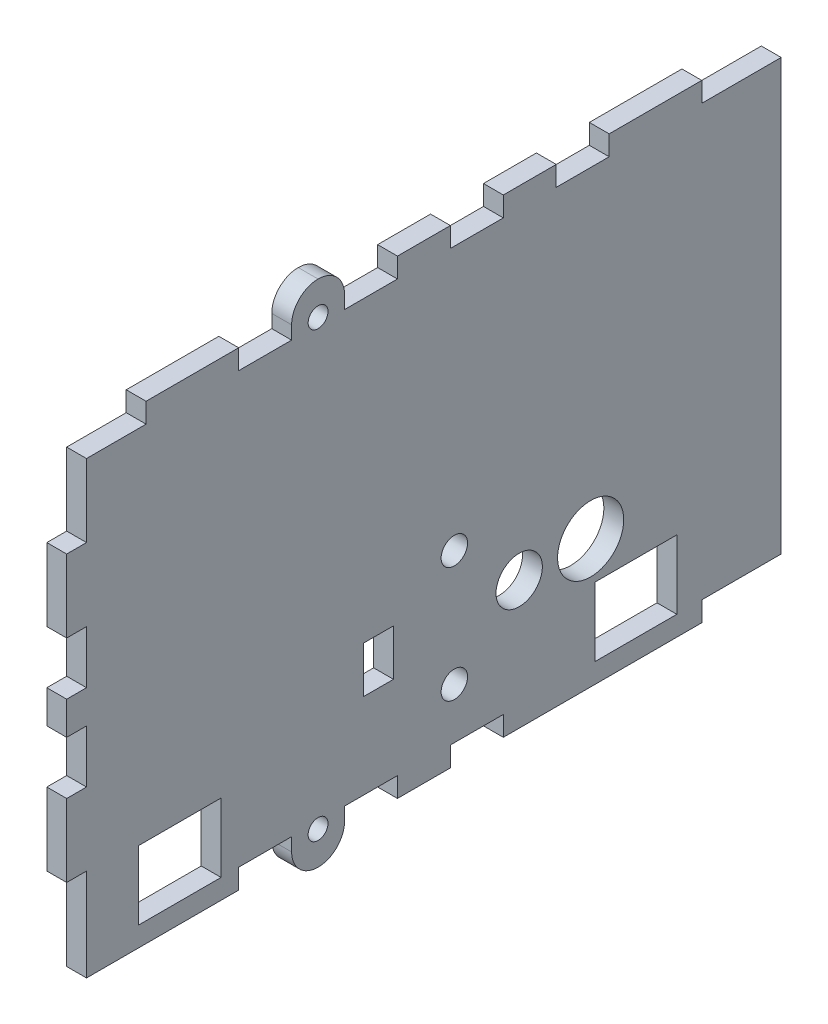
SolidWorks part; units mm, degrees
material "Balsa"
ref_plane "Alzado" through (0, 0, 0) normal (0, 0, 1) x (1, 0, 0)
ref_plane "Planta" through (0, 0, 0) normal (0, 1, 0) x (1, 0, 0)
ref_plane "Vista lateral" through (0, 0, 0) normal (1, 0, 0) x (0, 0, -1)
sketch "Croquis1" plane through (0, 0, 0) normal (1, 0, 0) x (0, 0, -1)
  line L1 (-54, -35.5) -> (54, -35.5)
  line L2 (-54, -35.5) -> (-54, 35.5)
  line L3 (-54, 35.5) -> (54, 35.5)
  line L4 (54, -35.5) -> (54, 35.5)
  line L5 (-54, -35.5) -> (54, 35.5) construction
  line L6 (-54, 35.5) -> (54, -35.5) construction
  point P0 (0, 0)
  dimension "D1" = 108
  dimension "D2" = 71
extrude "Saliente-Extruir1" add sketch "Croquis1" along normal mid plane 3
sketch "Croquis2" plane through (-1.5, 0, 0) normal (-1, 0, 0) x (0, 0, 1)
  line L1 (-42, -32.5) -> (-54, -32.5)
  line L2 (-42, -32.5) -> (-42, -35.5)
  line L3 (-42, -35.5) -> (-54, -35.5)
  line L4 (-54, -32.5) -> (-54, -35.5)
  line L9 (-12, -32.5) -> (-4, -32.5)
  line L25 (-54, 0) -> (54, 0) construction
  line L30 (-54, -35.5) -> (-54, 35.5) construction
  line L31 (54, 35.5) -> (54, -35.5) construction
  line L32 (54, 32.5) -> (54, 35.5)
  line L33 (42, 35.5) -> (54, 35.5)
  line L34 (42, 32.5) -> (42, 35.5)
  line L35 (42, 32.5) -> (54, 32.5)
  line L36 (28, 32.5) -> (28, 35.5)
  line L37 (20, 35.5) -> (28, 35.5)
  line L38 (20, 32.5) -> (20, 35.5)
  line L39 (20, 32.5) -> (28, 32.5)
  line L40 (12, 32.5) -> (12, 35.5)
  line L41 (4, 35.5) -> (12, 35.5)
  line L42 (4, 32.5) -> (4, 35.5)
  line L43 (4, 32.5) -> (12, 32.5)
  line L44 (-4, 32.5) -> (-4, 35.5)
  line L45 (-12, 35.5) -> (-4, 35.5)
  line L46 (-12, 32.5) -> (-12, 35.5)
  line L47 (-12, 32.5) -> (-4, 32.5)
  line L48 (-20, 32.5) -> (-20, 35.5)
  line L49 (-28, 35.5) -> (-20, 35.5)
  line L50 (-28, 32.5) -> (-28, 35.5)
  line L51 (-28, 32.5) -> (-20, 32.5)
  line L52 (-54, 32.5) -> (-54, 35.5)
  line L53 (-42, 35.5) -> (-54, 35.5)
  line L54 (-42, 32.5) -> (-42, 35.5)
  line L55 (-42, 32.5) -> (-54, 32.5)
  line L56 (-12, -32.5) -> (-12, -35.5)
  line L57 (-12, -35.5) -> (-4, -35.5)
  line L58 (-4, -32.5) -> (-4, -35.5)
  line L59 (4, -32.5) -> (12, -32.5)
  line L60 (4, -32.5) -> (4, -35.5)
  line L61 (4, -35.5) -> (12, -35.5)
  line L62 (12, -32.5) -> (12, -35.5)
  line L63 (20, -32.5) -> (28, -32.5)
  line L64 (20, -32.5) -> (20, -35.5)
  line L65 (20, -35.5) -> (28, -35.5)
  line L66 (28, -32.5) -> (28, -35.5)
extrude "Cortar-Extruir1" cut sketch "Croquis2" against normal blind 3
sketch "Croquis6" plane through (-1.5, 0, 0) normal (-1, 0, 0) x (0, 0, 1)
  line L0 (54, 32.5) -> (54, -35.5) construction
  line L1 (51, -21.5) -> (54, -21.5)
  line L2 (51, -21.5) -> (51, -35.5)
  line L3 (51, -35.5) -> (54, -35.5)
  line L4 (54, -21.5) -> (54, -35.5)
  line L5 (51, -2.5) -> (54, -2.5)
  line L6 (51, -2.5) -> (51, -10.5)
  line L7 (51, -10.5) -> (54, -10.5)
  line L8 (54, -2.5) -> (54, -10.5)
  line L9 (51, -10.5) -> (54, -10.5) construction
  line L10 (51, 10.5) -> (54, 10.5) construction
  line L11 (51, 2.5) -> (54, 2.5)
  line L12 (51, 2.5) -> (51, 10.5)
  line L13 (51, 10.5) -> (54, 10.5)
  line L14 (54, 2.5) -> (54, 10.5)
  line L16 (51, 21.5) -> (54, 21.5)
  line L17 (51, 21.5) -> (51, 35.5)
  line L18 (51, 35.5) -> (54, 35.5)
  line L19 (54, 21.5) -> (54, 35.5)
extrude "Cortar-Extruir3" cut sketch "Croquis6" against normal blind 3
sketch "Croquis8" plane through (-1.5, 0, 0) normal (-1, 0, 0) x (0, 0, 1)
  line L1 (12, 35.5) -> (20, 35.5)
  line L2 (12, 35.5) -> (12, 38.5)
  line L3 (12, 38.5) -> (20, 38.5)
  line L4 (20, 35.5) -> (20, 38.5)
  dimension "D1" = 3
extrude "Saliente-Extruir2" add sketch "Croquis8" against normal blind 3
fillet "Redondeo2" radius 4 2 edges at (0, 38.5, 20) (0, 38.5, 12)
sketch "Croquis9" plane through (-1.5, 0, 0) normal (-1, 0, 0) x (0, 0, 1)
  line L0 (12, 33.5) -> (20, 33.5) construction
  line L1 (12, 32.5) -> (12, 34.5) construction
  line L2 (20, 34.5) -> (20, 32.5) construction
  circle A0 centre (16, 33.5) radius 1.5
  dimension "D1" = 3
extrude "Cortar-Extruir5" cut sketch "Croquis9" against normal blind 3
mirror "Simetría1" about plane through (0, 0, 0) normal (0, 1, 0) of "Redondeo2", "Cortar-Extruir5", "Saliente-Extruir2"
sketch "Croquis12" plane through (-1.5, 0, 0) normal (-1, 0, 0) x (0, 0, 1)
  line L5 (43.1407, -22.1055) -> (30.6593, -22.1055)
  line L6 (43.1407, -22.1055) -> (43.1407, -32.5055)
  line L7 (43.1407, -32.5055) -> (30.6593, -32.5055)
  line L8 (30.6593, -22.1055) -> (30.6593, -32.5055)
  line L9 (-38.2299, -32.5055) -> (-25.8739, -32.5055)
  line L10 (-38.2299, -32.5055) -> (-38.2299, -22.1055)
  line L11 (-38.2299, -22.1055) -> (-25.8739, -22.1055)
  line L12 (-25.8739, -32.5055) -> (-25.8739, -22.1055)
  dimension "D1" = 10.4
  dimension "D2" = 10.4
extrude "Cortar-Extruir7" cut sketch "Croquis12" against normal blind 10
sketch "Croquis10" plane through (-1.5, 0, 0) normal (-1, 0, 0) x (0, 0, 1)
  line L0 (-25.2, -16.1) -> (9.1, -16.1) construction
  line L1 (4.6, -19.6) -> (9.1, -19.6)
  line L2 (4.6, -19.6) -> (4.6, -12.6)
  line L3 (4.6, -12.6) -> (9.1, -12.6)
  line L4 (9.1, -19.6) -> (9.1, -12.6)
  line L5 (-4.6, -24.85) -> (-4.6, -16.1) construction
  line L6 (-4.6, -16.1) -> (-4.6, -7.35) construction
  line L7 (-25.2, -49.1) -> (-59.5051, -49.1) construction
  line L8 (-25.8739, -32.5055) -> (-38.2299, -22.1055) construction
  line L12 (-42, -32.5) -> (-54, -32.5) construction
  circle A0 centre (-25.2, -16.1) radius 4.6
  circle A1 centre (-14.4, -16.1) radius 3.5
  circle A2 centre (-4.6, -24.85) radius 2
  circle A3 centre (-4.6, -7.35) radius 2
  dimension "D5" = 4
  dimension "D6" = 4
  dimension "D12" = 8.75
  dimension "D1" = 17.5
  dimension "D2" = 9.2
  dimension "D3" = 4.5
  dimension "D4" = 7
  dimension "D7" = 20.6
  dimension "D8" = 9.8
  dimension "D9" = 4.6
  dimension "D11" = 33
  dimension "20" = 16.4
extrude "Cortar-Extruir6" cut sketch "Croquis10" against normal blind 10 contours A0 | A1 | A1 | A2 | L1 L4 L3 L2 | A3 region at (-1.5, -16.1, 6.85) region at (-1.5, -16.1, -25.2) region at (-1.5, -16.1, -14.4) region at (-1.5, -24.85, -4.6)
sketch "Croquis14" plane through (1.5, 0, 0) normal (1, 0, 0) x (0, 0, -1)
  line L48 (-20, -32.5) -> (-20, -34.5)
  line L49 (-12, -34.5) -> (-12, -32.5)
  line L50 (-12, -32.5) -> (-4, -32.5)
  line L51 (-4, -32.5) -> (-4, -35.5)
  line L52 (-4, -35.5) -> (4, -35.5)
  line L53 (4, -35.5) -> (4, -32.5)
  line L54 (4, -32.5) -> (12, -32.5)
  line L55 (12, -32.5) -> (12, -35.5)
  line L56 (12, -35.5) -> (42, -35.5)
  line L57 (42, -35.5) -> (42, -32.5)
  line L58 (42, -32.5) -> (54, -32.5)
  line L59 (54, -32.5) -> (54, 32.5)
  line L60 (54, 32.5) -> (42, 32.5)
  line L61 (42, 32.5) -> (42, 35.5)
  line L62 (42, 35.5) -> (28, 35.5)
  line L63 (28, 35.5) -> (28, 32.5)
  line L64 (28, 32.5) -> (20, 32.5)
  line L65 (20, 32.5) -> (20, 35.5)
  line L66 (20, 35.5) -> (12, 35.5)
  line L67 (12, 35.5) -> (12, 32.5)
  line L68 (12, 32.5) -> (4, 32.5)
  line L69 (4, 32.5) -> (4, 35.5)
  line L70 (4, 35.5) -> (-4, 35.5)
  line L71 (-4, 35.5) -> (-4, 32.5)
  line L72 (-4, 32.5) -> (-12, 32.5)
  line L73 (-12, 32.5) -> (-12, 34.5)
  line L74 (-20, 34.5) -> (-20, 32.5)
  line L75 (-20, 32.5) -> (-28, 32.5)
  line L76 (-28, 32.5) -> (-28, 35.5)
  line L77 (-28, 35.5) -> (-42, 35.5)
  line L78 (-42, 35.5) -> (-42, 32.5)
  line L79 (-42, 32.5) -> (-51, 32.5)
  line L80 (-51, 32.5) -> (-51, 21.5)
  line L81 (-51, 21.5) -> (-54, 21.5)
  line L82 (-54, 21.5) -> (-54, 10.5)
  line L83 (-54, 10.5) -> (-51, 10.5)
  line L84 (-51, 10.5) -> (-51, 2.5)
  line L85 (-51, 2.5) -> (-54, 2.5)
  line L86 (-54, 2.5) -> (-54, -2.5)
  line L87 (-54, -2.5) -> (-51, -2.5)
  line L88 (-51, -2.5) -> (-51, -10.5)
  line L89 (-51, -10.5) -> (-54, -10.5)
  line L90 (-54, -10.5) -> (-54, -21.5)
  line L91 (-54, -21.5) -> (-51, -21.5)
  line L92 (-51, -21.5) -> (-51, -35.5)
  line L93 (-51, -35.5) -> (-28, -35.5)
  line L94 (-28, -35.5) -> (-28, -32.5)
  line L95 (-28, -32.5) -> (-20, -32.5)
  line L96 (-20, -32.5) -> (-20, -34.5)
  line L97 (-12, -34.5) -> (-12, -32.5)
  line L98 (-12, -32.5) -> (-4, -32.5)
  line L99 (-4, -32.5) -> (-4, -35.5)
  line L100 (-4, -35.5) -> (4, -35.5)
  line L101 (4, -35.5) -> (4, -32.5)
  line L102 (4, -32.5) -> (12, -32.5)
  line L103 (12, -32.5) -> (12, -35.5)
  line L104 (12, -35.5) -> (42, -35.5)
  line L105 (42, -35.5) -> (42, -32.5)
  line L106 (42, -32.5) -> (54, -32.5)
  line L107 (54, -32.5) -> (54, 32.5)
  line L108 (54, 32.5) -> (42, 32.5)
  line L109 (42, 32.5) -> (42, 35.5)
  line L110 (42, 35.5) -> (28, 35.5)
  line L111 (28, 35.5) -> (28, 32.5)
  line L112 (28, 32.5) -> (20, 32.5)
  line L113 (20, 32.5) -> (20, 35.5)
  line L114 (20, 35.5) -> (12, 35.5)
  line L115 (12, 35.5) -> (12, 32.5)
  line L116 (12, 32.5) -> (4, 32.5)
  line L117 (4, 32.5) -> (4, 35.5)
  line L118 (4, 35.5) -> (-4, 35.5)
  line L119 (-4, 35.5) -> (-4, 32.5)
  line L120 (-4, 32.5) -> (-12, 32.5)
  line L121 (-12, 32.5) -> (-12, 34.5)
  line L122 (-20, 34.5) -> (-20, 32.5)
  line L123 (-20, 32.5) -> (-28, 32.5)
  line L124 (-28, 32.5) -> (-28, 35.5)
  line L125 (-28, 35.5) -> (-42, 35.5)
  line L126 (-42, 35.5) -> (-42, 32.5)
  line L127 (-42, 32.5) -> (-51, 32.5)
  line L128 (-51, 32.5) -> (-51, 21.5)
  line L129 (-51, 21.5) -> (-54, 21.5)
  line L130 (-54, 21.5) -> (-54, 10.5)
  line L131 (-54, 10.5) -> (-51, 10.5)
  line L132 (-51, 10.5) -> (-51, 2.5)
  line L133 (-51, 2.5) -> (-54, 2.5)
  line L134 (-54, 2.5) -> (-54, -2.5)
  line L135 (-54, -2.5) -> (-51, -2.5)
  line L136 (-51, -2.5) -> (-51, -10.5)
  line L137 (-51, -10.5) -> (-54, -10.5)
  line L138 (-54, -10.5) -> (-54, -21.5)
  line L139 (-54, -21.5) -> (-51, -21.5)
  line L140 (-51, -21.5) -> (-51, -35.5)
  line L141 (-51, -35.5) -> (-28, -35.5)
  line L142 (-28, -35.5) -> (-28, -32.5)
  line L143 (-28, -32.5) -> (-20, -32.5)
  circle A0 centre (21.1618, -13.9126) radius 0.0074
  circle A1 centre (25.2, -16.1) radius 5
  arc A5 (-20, -34.5) -> (-16, -38.5) centre (-16, -34.5) ccw
  arc A6 (-16, -38.5) -> (-12, -34.5) centre (-16, -34.5) ccw
  arc A7 (-12, 34.5) -> (-16, 38.5) centre (-16, 34.5) ccw
  arc A8 (-16, 38.5) -> (-20, 34.5) centre (-16, 34.5) ccw
  arc A9 (-20, -34.5) -> (-16, -38.5) centre (-16, -34.5) ccw
  arc A10 (-16, -38.5) -> (-12, -34.5) centre (-16, -34.5) ccw
  arc A11 (-12, 34.5) -> (-16, 38.5) centre (-16, 34.5) ccw
  arc A12 (-16, 38.5) -> (-20, 34.5) centre (-16, 34.5) ccw
  dimension "D2" = 10
  dimension "D1" = 0
extrude "Cortar-Extruir9" cut sketch "Croquis14" against normal blind 10 contours A1 A0 region at (1.5, -16.1, -25.2)
sketch "Croquis15" plane through (-1.5, 0, 0) normal (-1, 0, 0) x (0, 0, 1)
  line L0 (-32.1325, -26.6394) -> (-32.1325, -20.6621)
  line L2 (-32.1325, -33.446) -> (-32.1325, -26.9394)
  line L4 (-31.8325, -33.446) -> (-31.8325, -26.9394)
  line L5 (36.9382, -26.7273) -> (36.9382, -20.75)
  line L6 (36.9382, -33.534) -> (36.9382, -27.0273)
  line L7 (-39.6781, -26.9394) -> (-24.5, -26.9394)
  line L9 (-39.6781, -26.6394) -> (-24.5, -26.6394)
  line L11 (-32.1325, -26.7902) -> (-31.9762, -26.7872) construction
  line L12 (-32.1325, -26.7885) -> (-31.8325, -26.7945) construction
  line L13 (-31.9888, -26.7874) -> (-31.9887, -26.7914) construction
  line L14 (37.2382, -33.534) -> (37.2382, -27.0273)
  line L15 (-31.8325, -26.6394) -> (-31.8325, -20.6621)
  line L16 (-31.8325, -26.7945) -> (-31.8325, -26.7843)
  line L17 (-31.9764, -26.7916) -> (-31.9762, -26.7872) construction
  line L18 (29.3926, -27.0273) -> (44.5707, -27.0273)
  line L19 (-32.1325, -26.7902) -> (-32.1325, -26.7885)
  line L20 (29.3926, -26.7273) -> (44.5707, -26.7273)
  line L21 (36.9382, -26.8782) -> (37.0945, -26.8751) construction
  line L22 (36.9382, -26.8765) -> (37.2382, -26.8824) construction
  line L23 (37.082, -26.8753) -> (37.0821, -26.8793) construction
  line L24 (37.2382, -26.7273) -> (37.2382, -20.75)
  line L25 (37.2382, -26.8824) -> (37.2382, -26.8723)
  line L26 (37.0944, -26.8796) -> (37.0945, -26.8751) construction
  line L27 (36.9382, -26.8782) -> (36.9382, -26.8765)
  line L28 (6.8787, -15.4888) -> (6.8787, -9.5115)
  line L29 (6.8787, -22.2954) -> (6.8787, -15.7888)
  line L30 (7.1787, -22.2954) -> (7.1787, -15.7888)
  line L31 (-0.6669, -15.7888) -> (14.5112, -15.7888)
  line L32 (-0.6669, -15.4888) -> (14.5112, -15.4888)
  line L33 (6.8787, -15.6396) -> (7.0349, -15.6366) construction
  line L34 (6.8787, -15.6379) -> (7.1787, -15.6439) construction
  line L35 (7.0224, -15.6368) -> (7.0225, -15.6408) construction
  line L36 (7.1787, -15.4888) -> (7.1787, -9.5115)
  line L37 (7.1787, -15.6439) -> (7.1787, -15.6337)
  line L38 (7.0348, -15.641) -> (7.0349, -15.6366) construction
  line L39 (6.8787, -15.6396) -> (6.8787, -15.6379)
  line L40 (-4.5776, -6.8) -> (-4.5776, -0.8227)
  line L41 (-4.5776, -13.6066) -> (-4.5776, -7.1)
  line L42 (-4.2776, -13.6066) -> (-4.2776, -7.1)
  line L43 (-12.1233, -7.1) -> (3.0549, -7.1)
  line L44 (-12.1233, -6.8) -> (3.0549, -6.8)
  line L45 (-4.5776, -6.9509) -> (-4.4214, -6.9478) construction
  line L46 (-4.5776, -6.9491) -> (-4.2776, -6.9551) construction
  line L47 (-4.4339, -6.948) -> (-4.4338, -6.952) construction
  line L48 (-4.2776, -6.8) -> (-4.2776, -0.8227)
  line L49 (-4.2776, -6.9551) -> (-4.2776, -6.9449)
  line L50 (-4.4215, -6.9522) -> (-4.4214, -6.9478) construction
  line L51 (-4.5776, -6.9509) -> (-4.5776, -6.9491)
  line L52 (-4.8351, -24.4994) -> (-4.8351, -18.5221)
  line L53 (-4.8351, -31.306) -> (-4.8351, -24.7994)
  line L54 (-4.5351, -31.306) -> (-4.5351, -24.7994)
  line L55 (-12.3807, -24.7994) -> (2.7974, -24.7994)
  line L56 (-12.3807, -24.4994) -> (2.7974, -24.4994)
  line L57 (-4.8351, -24.6502) -> (-4.6788, -24.6471) construction
  line L58 (-4.8351, -24.6485) -> (-4.5351, -24.6544) construction
  line L59 (-4.6913, -24.6474) -> (-4.6913, -24.6514) construction
  line L60 (-4.5351, -24.4994) -> (-4.5351, -18.5221)
  line L61 (-4.5351, -24.6544) -> (-4.5351, -24.6443)
  line L62 (-4.6789, -24.6516) -> (-4.6788, -24.6471) construction
  line L63 (-4.8351, -24.6502) -> (-4.8351, -24.6485)
  line L64 (-14.618, -15.5531) -> (-14.618, -9.5758)
  line L65 (-14.618, -22.3598) -> (-14.618, -15.8531)
  line L66 (-14.318, -22.3598) -> (-14.318, -15.8531)
  line L67 (-22.1636, -15.8531) -> (-6.9855, -15.8531)
  line L68 (-22.1636, -15.5531) -> (-6.9855, -15.5531)
  line L69 (-14.618, -15.704) -> (-14.4618, -15.7009) construction
  line L70 (-14.618, -15.7023) -> (-14.318, -15.7082) construction
  line L71 (-14.4743, -15.7012) -> (-14.4742, -15.7051) construction
  line L72 (-14.318, -15.5531) -> (-14.318, -9.5758)
  line L73 (-14.318, -15.7082) -> (-14.318, -15.6981)
  line L74 (-14.4619, -15.7054) -> (-14.4618, -15.7009) construction
  line L75 (-14.618, -15.704) -> (-14.618, -15.7023)
  line L76 (-25.6197, -15.7627) -> (-25.6197, -9.7854)
  line L77 (-25.6197, -22.5694) -> (-25.6197, -16.0627)
  line L78 (-25.3197, -22.5694) -> (-25.3197, -16.0627)
  line L79 (-33.1653, -16.0627) -> (-17.9872, -16.0627)
  line L80 (-33.1653, -15.7627) -> (-17.9872, -15.7627)
  line L81 (-25.6197, -15.9136) -> (-25.4634, -15.9105) construction
  line L82 (-25.6197, -15.9119) -> (-25.3197, -15.9178) construction
  line L83 (-25.4759, -15.9107) -> (-25.4758, -15.9147) construction
  line L84 (-25.3197, -15.7627) -> (-25.3197, -9.7854)
  line L85 (-25.3197, -15.9178) -> (-25.3197, -15.9076)
  line L86 (-25.4635, -15.9149) -> (-25.4634, -15.9105) construction
  line L87 (-25.6197, -15.9136) -> (-25.6197, -15.9119)
  point P0 (-31.9825, -27.054)
  point P5 (-32.0519, -17.979)
  point P10 (-32.2677, -25.9378)
  point P11 (-32.0519, -33.943)
  point P12 (-39.6781, -26.4604)
  point P13 (-24.5, -26.7894)
  point P14 (-31.8922, -20.6621)
  point P15 (-32.0519, -33.446)
  point P18 (37.0882, -27.142)
  point P49 (7.0287, -15.9034)
  point P70 (-4.4276, -7.2147)
  point P91 (-4.6851, -24.914)
  point P112 (-14.468, -15.9678)
  point P133 (-25.4697, -16.1774)
  dimension "D1" = 0.3
  dimension "D2" = 0.3
  dimension "D3" = 0.3
  dimension "D4" = 0.3
  dimension "D5" = 0.3
  dimension "D6" = 0.3
  dimension "D7" = 0.3
  dimension "D8" = 0.3
